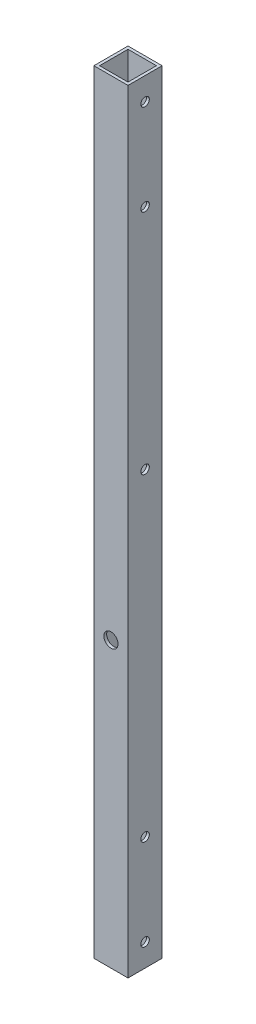
SolidWorks part; units mm, degrees
material "6061 Alloy"
ref_plane "Front Plane" through (0, 0, 0) normal (0, 0, 1) x (1, 0, 0)
ref_plane "Top Plane" through (0, 0, 0) normal (0, 1, 0) x (1, 0, 0)
ref_plane "Right Plane" through (0, 0, 0) normal (1, 0, 0) x (0, 0, -1)
sketch "Sketch1" plane through (0, 0, 0) normal (0, 1, 0) x (1, 0, 0)
  line L1 (-9.525, -9.525) -> (9.525, -9.525)
  line L2 (-9.525, -9.525) -> (-9.525, 9.525)
  line L3 (-9.525, 9.525) -> (9.525, 9.525)
  line L4 (9.525, -9.525) -> (9.525, 9.525)
  line L5 (-9.525, -9.525) -> (9.525, 9.525) construction
  line L6 (-9.525, 9.525) -> (9.525, -9.525) construction
  line L7 (-7.9375, 7.9375) -> (7.9375, 7.9375)
  line L8 (-7.9375, 7.9375) -> (-7.9375, -7.9375)
  line L9 (-7.9375, -7.9375) -> (7.9375, -7.9375)
  line L10 (7.9375, 7.9375) -> (7.9375, -7.9375)
  line L11 (-7.9375, 7.9375) -> (7.9375, -7.9375) construction
  line L12 (-7.9375, -7.9375) -> (7.9375, 7.9375) construction
  point P0 (0, 0)
  point P6 (0, 0)
  dimension "D1" = 19.05
  dimension "D2" = 19.05
  dimension "D3" = 1.5875
  dimension "D4" = 1.5875
extrude "Boss-Extrude1" add sketch "Sketch1" along normal blind 431.8
ref_plane "Plane1" through (0, 215.9, 0) normal (0, -1, 0) x (-1, 0, 0)
ref_axis "Axis1" through (0, 215.9, -10.4775) along (0, 0, 1)
sketch "Sketch2" plane through (0, 0, 9.525) normal (0, 0, 1) x (1, 0, 0)
  line L0 (0, 0) -> (0, 158.75) construction
  line L1 (-9.525, 0) -> (9.525, 0) construction
  circle A2 centre (0, 158.75) radius 3.9687
extrude "Cut-Extrude1" cut sketch "Sketch2" against normal up to next
sketch "Sketch3" plane through (0, 0, 0) normal (1, 0, 0) x (0, 0, -1)
  line L0 (0, 0) -> (0, 12.7) construction
  line L1 (0, 12.7) -> (0, 63.5) construction
  line L2 (0, 63.5) -> (0, 241.3) construction
  line L3 (0, 241.3) -> (0, 368.3) construction
  line L4 (0, 368.3) -> (0, 419.1) construction
  circle A0 centre (0, 12.7) radius 2.3813
  circle A1 centre (0, 63.5) radius 2.3812
  circle A2 centre (0, 241.3) radius 2.3812
  circle A3 centre (0, 368.3) radius 2.3813
  circle A4 centre (0, 419.1) radius 2.3813
extrude "Cut-Extrude2" cut sketch "Sketch3" against normal through all both and the other way through all
